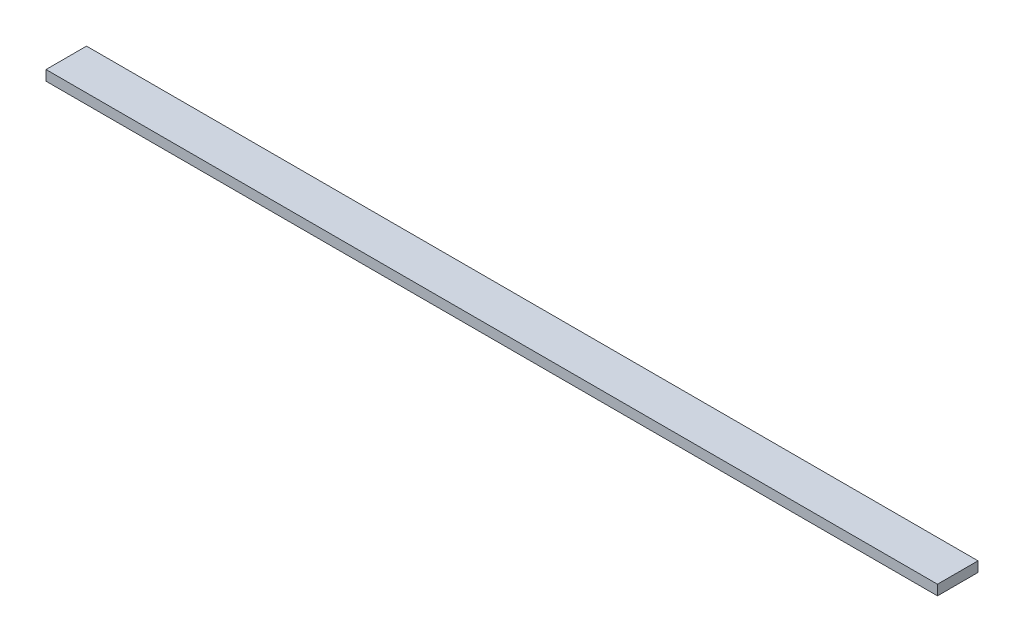
SolidWorks part; units mm, degrees
ref_plane "Front Plane" through (0, 0, 0) normal (0, 0, 1) x (1, 0, 0)
ref_plane "Top Plane" through (0, 0, 0) normal (0, 1, 0) x (1, 0, 0)
ref_plane "Right Plane" through (0, 0, 0) normal (1, 0, 0) x (0, 0, -1)
sketch "Sketch1" plane through (0, 0, 0) normal (0, 1, 0) x (1, 0, 0)
  line L1 (0, 0) -> (558.8, 0)
  line L2 (0, 0) -> (0, 25.4)
  line L3 (0, 25.4) -> (558.8, 25.4)
  line L4 (558.8, 0) -> (558.8, 25.4)
  dimension "D1" = 25.4
  dimension "D2" = 558.8
extrude "Boss-Extrude1" add sketch "Sketch1" along normal blind 6.35
